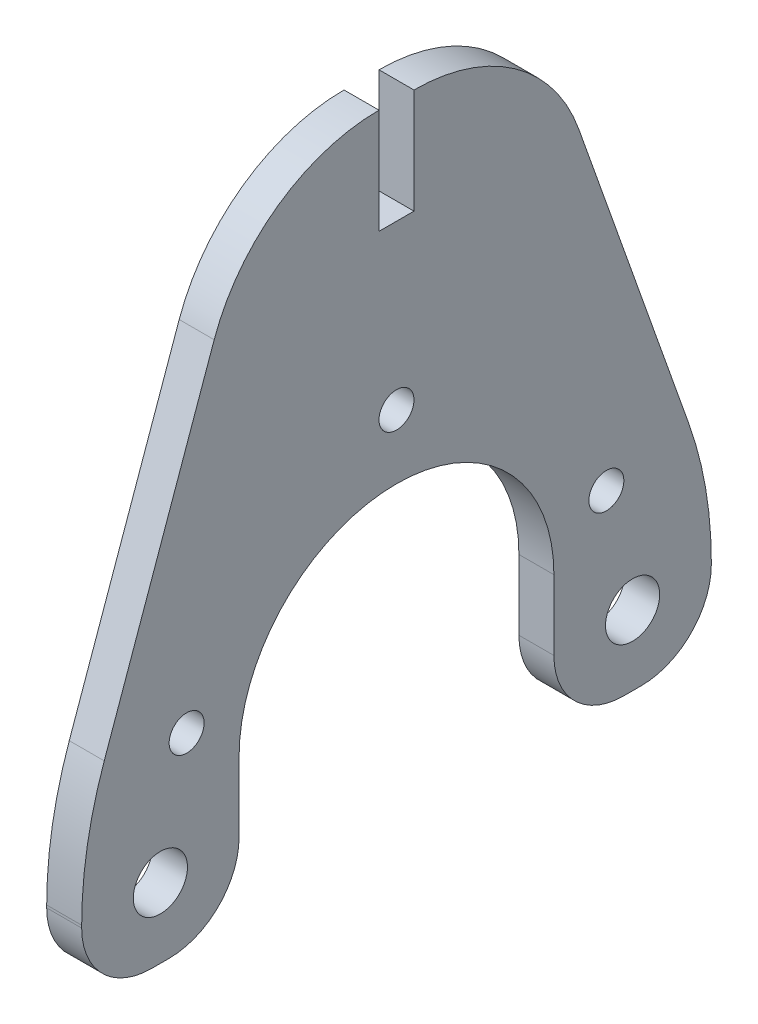
SolidWorks part; units mm, degrees
material "6061 Alloy"
ref_plane "Front Plane" through (0, 0, 0) normal (0, 0, 1) x (1, 0, 0)
ref_plane "Top Plane" through (0, 0, 0) normal (0, 1, 0) x (1, 0, 0)
ref_plane "Right Plane" through (0, 0, 0) normal (1, 0, 0) x (0, 0, -1)
sketch "Sketch1" plane through (0, 0, 0) normal (1, 0, 0) x (0, 0, -1)
  line L0 (1.5875, 44.45) -> (1.5875, 34.925)
  line L1 (1.5875, 34.925) -> (-1.5875, 34.925)
  line L2 (0, 0) -> (0, 73.524) construction
  line L3 (-1.5875, 44.45) -> (-1.5875, 34.925)
  line L4 (21.4312, -6.35) -> (-21.4312, -6.35) construction
  line L5 (16.5481, 33.885) -> (28.575, 0)
  line L6 (-16.5481, 33.885) -> (-28.575, 0)
  line L7 (28.575, 0) -> (28.575, -12.7)
  line L8 (28.575, -12.7) -> (14.2875, -12.7)
  line L9 (14.2875, -12.7) -> (14.2875, 0)
  line L10 (-14.2875, 0) -> (-14.2875, -12.7)
  line L11 (-14.2875, -12.7) -> (-28.575, -12.7)
  line L12 (-28.575, -12.7) -> (-28.575, 0)
  arc A0 (14.2875, 0) -> (-14.2875, 0) centre (0, 0) ccw
  arc A5 (16.5481, 33.885) -> (1.5875, 44.45) centre (1.5875, 28.575) ccw
  arc A10 (-16.5481, 33.885) -> (-1.5875, 44.45) centre (-1.5875, 28.575) cw
  circle A11 centre (21.4312, -6.35) radius 2.5797 construction
  circle A12 centre (-21.4312, -6.35) radius 2.5797 construction
  point P1 (0, -6.35)
  point P9 (21.4312, -12.7)
  point P18 (0, 34.925)
  dimension "D1" = 28.575
  dimension "D3" = 57.15
  dimension "D4" = 15.875
  dimension "D5" = 12.7
  dimension "D6" = 42.8625
  dimension "D7" = 14.2875
  dimension "D9" = 5.1594
  dimension "D2" = 3.175
  dimension "D10" = 6.35
  dimension "D12" = 9.525
extrude "Boss-Extrude1" add sketch "Sketch1" along normal blind 3.175
hole_wizard "#10 (0.1935) Diameter Hole1" positions "Sketch2" profile "Sketch3" hole size "#10" standard "ANSI Inch"
sketch "Sketch2" plane through (0, 0, 0) normal (-1, 0, 0) x (0, 0, 1)
  line L2 (-21.4312, -6.35) -> (21.4312, -6.35) construction
  point P0 (-21.4312, -6.35)
  point P2 (21.4312, -6.35)
  point P29 (0, -6.35)
  dimension "D1" = 42.8625
  dimension "D2" = 6.35
sketch "Sketch3" plane through (0, -6.35, -21.4312) normal (0, 1, 0) x (0, 0, 1)
  line L0 (0, 0) -> (0, 20.4786)
  line L1 (0, 20.4786) -> (2.4574, 19.002)
  line L2 (2.4574, 19.002) -> (2.4574, 0)
  line L5 (2.4574, 0) -> (0, 0)
  line L10 (0, 20.4786) -> (-2.4574, 19.002) construction
  line L11 (0, -6.35) -> (0, 107.95) construction
  dimension "Hole Dia." = 4.9149
  dimension "Hole Depth" = 19.002
  dimension "Drill Angle" = 118
sketch "Sketch4" plane through (3.175, 0, 0) normal (1, 0, 0) x (0, 0, -1)
  circle A6 centre (0, 20.0978) radius 1.5875 construction
  circle A7 centre (0, 20.0978) radius 1.5875
  circle A8 centre (-19.0489, 4.2227) radius 1.5875 construction
  circle A9 centre (-19.0489, 4.2227) radius 1.5875
  circle A10 centre (19.0489, 4.2228) radius 1.5875 construction
  circle A11 centre (19.0489, 4.2228) radius 1.5875
extrude "Cut-Extrude1" cut sketch "Sketch4" against normal through all
fillet "Fillet2" radius 35.56 2 edges at (1.5875, 0, 28.575) (1.5875, 0, -28.575)
fillet "Fillet1" radius 6.35 4 edges at (1.5875, -12.7, -28.575) (1.5875, -12.7, -14.2875) (1.5875, -12.7, 28.575) (1.5875, -12.7, 14.2875)
